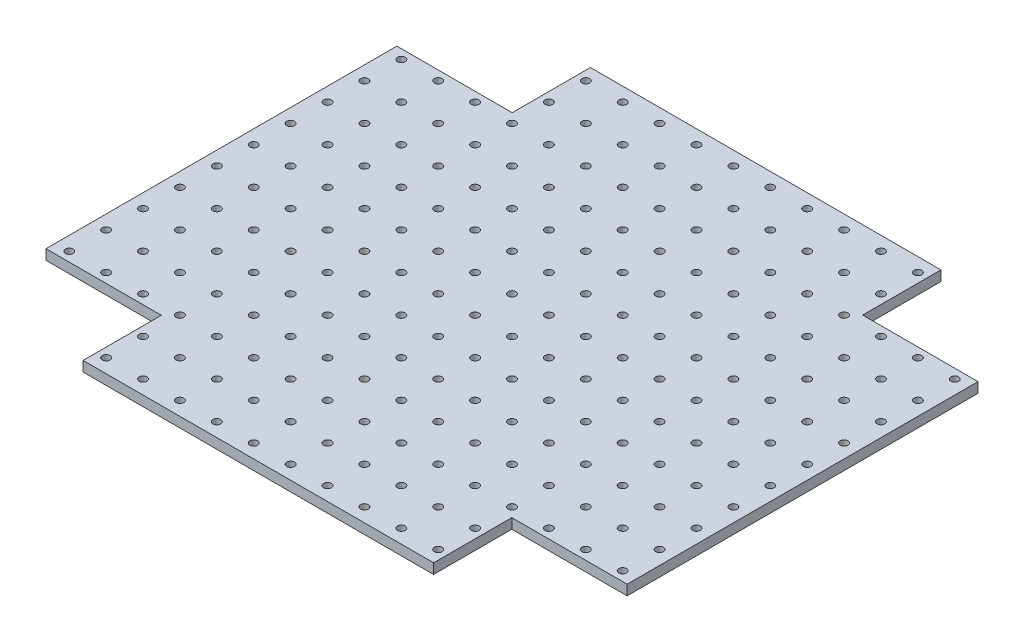
SolidWorks part; units mm, degrees
ref_plane "Front Plane" through (0, 0, 0) normal (0, 0, 1) x (1, 0, 0)
ref_plane "Top Plane" through (0, 0, 0) normal (0, 1, 0) x (1, 0, 0)
ref_plane "Right Plane" through (0, 0, 0) normal (1, 0, 0) x (0, 0, -1)
sketch "Sketch1" plane through (0, 0, 0) normal (0, 1, 0) x (1, 0, 0)
  line L0 (95, -95.1) -> (157.5, -95.1)
  line L1 (-157.5, 95.1) -> (-95, 95.1)
  line L2 (-157.5, 95.1) -> (-157.5, -95.1)
  line L3 (-157.5, -95.1) -> (-95, -95.1)
  line L4 (157.5, 95.1) -> (157.5, -95.1)
  line L5 (-157.5, 95.1) -> (157.5, -95.1) construction
  line L6 (-157.5, -95.1) -> (157.5, 95.1) construction
  line L7 (95, 137.5) -> (-95, 137.5)
  line L8 (95, 137.5) -> (95, 95.1)
  line L9 (95, -137.5) -> (-95, -137.5)
  line L10 (-95, 137.5) -> (-95, 95.1)
  line L11 (95, 137.5) -> (-95, -137.5) construction
  line L12 (95, -137.5) -> (-95, 137.5) construction
  line L13 (95, -95.1) -> (95, -137.5)
  line L14 (-95, -95.1) -> (-95, -137.5)
  line L15 (95, 95.1) -> (157.5, 95.1)
  point P0 (0, 0)
  point P6 (0, 0)
  dimension "D1" = 315
  dimension "D2" = 42.4
  dimension "D3" = 275
  dimension "D4" = 190
extrude "Boss-Extrude1" add sketch "Sketch1" along normal blind 5.4864
sketch "Sketch2" plane through (0, 5.4864, 0) normal (0, 1, 0) x (1, 0, 0)
  line L0 (0, 0) -> (150, 0) construction
  line L1 (150, 0) -> (150, -130) construction
  line L2 (150, -130) -> (130, -130) construction
  line L3 (150, -110) -> (130, -110) construction
  line L4 (150, -90) -> (130, -90) construction
  line L5 (150, -70) -> (130, -70) construction
  line L6 (150, -50) -> (130, -50) construction
  line L7 (150, -30) -> (130, -30) construction
  line L8 (150, -10) -> (130, -10) construction
  line L9 (150, 10) -> (130, 10) construction
  line L10 (150, 30) -> (130, 30) construction
  line L11 (150, 50) -> (130, 50) construction
  line L12 (150, 70) -> (130, 70) construction
  line L13 (150, 90) -> (130, 90) construction
  line L14 (150, 110) -> (130, 110) construction
  line L15 (150, -130) -> (150, -110) construction
  line L16 (150, 130) -> (130, 130) construction
  line L17 (150, 150) -> (130, 150) construction
  circle A0 centre (150, -130) radius 2.1 construction
  circle A1 centre (130, -130) radius 2.1 construction
  circle A2 centre (110, -130) radius 2.1 construction
  circle A3 centre (90, -130) radius 2.1
  circle A4 centre (70, -130) radius 2.1
  circle A5 centre (50, -130) radius 2.1
  circle A6 centre (30, -130) radius 2.1
  circle A7 centre (10, -130) radius 2.1
  circle A8 centre (-10, -130) radius 2.1
  circle A9 centre (-30, -130) radius 2.1
  circle A10 centre (-50, -130) radius 2.1
  circle A11 centre (-70, -130) radius 2.1
  circle A12 centre (-90, -130) radius 2.1
  circle A13 centre (-110, -130) radius 2.1
  circle A14 centre (-130, -130) radius 2.1 construction
  circle A15 centre (-150, -130) radius 2.1 construction
  circle A17 centre (150, -110) radius 2.1 construction
  circle A18 centre (130, -110) radius 2.1 construction
  circle A19 centre (110, -110) radius 2.1 construction
  circle A20 centre (90, -110) radius 2.1
  circle A21 centre (70, -110) radius 2.1
  circle A22 centre (50, -110) radius 2.1
  circle A23 centre (30, -110) radius 2.1
  circle A24 centre (10, -110) radius 2.1
  circle A25 centre (-10, -110) radius 2.1
  circle A26 centre (-30, -110) radius 2.1
  circle A27 centre (-50, -110) radius 2.1
  circle A28 centre (-70, -110) radius 2.1
  circle A29 centre (-90, -110) radius 2.1
  circle A30 centre (-110, -110) radius 2.1
  circle A31 centre (-130, -110) radius 2.1 construction
  circle A32 centre (-150, -110) radius 2.1 construction
  circle A34 centre (150, -90) radius 2.1
  circle A35 centre (130, -90) radius 2.1
  circle A36 centre (110, -90) radius 2.1
  circle A37 centre (90, -90) radius 2.1
  circle A38 centre (70, -90) radius 2.1
  circle A39 centre (50, -90) radius 2.1
  circle A40 centre (30, -90) radius 2.1
  circle A41 centre (10, -90) radius 2.1
  circle A42 centre (-10, -90) radius 2.1
  circle A43 centre (-30, -90) radius 2.1
  circle A44 centre (-50, -90) radius 2.1
  circle A45 centre (-70, -90) radius 2.1
  circle A46 centre (-90, -90) radius 2.1
  circle A47 centre (-110, -90) radius 2.1
  circle A48 centre (-130, -90) radius 2.1
  circle A49 centre (-150, -90) radius 2.1
  circle A51 centre (150, -70) radius 2.1
  circle A52 centre (130, -70) radius 2.1
  circle A53 centre (110, -70) radius 2.1
  circle A54 centre (90, -70) radius 2.1
  circle A55 centre (70, -70) radius 2.1
  circle A56 centre (50, -70) radius 2.1
  circle A57 centre (30, -70) radius 2.1
  circle A58 centre (10, -70) radius 2.1
  circle A59 centre (-10, -70) radius 2.1
  circle A60 centre (-30, -70) radius 2.1
  circle A61 centre (-50, -70) radius 2.1
  circle A62 centre (-70, -70) radius 2.1
  circle A63 centre (-90, -70) radius 2.1
  circle A64 centre (-110, -70) radius 2.1
  circle A65 centre (-130, -70) radius 2.1
  circle A66 centre (-150, -70) radius 2.1
  circle A68 centre (150, -50) radius 2.1
  circle A69 centre (130, -50) radius 2.1
  circle A70 centre (110, -50) radius 2.1
  circle A71 centre (90, -50) radius 2.1
  circle A72 centre (70, -50) radius 2.1
  circle A73 centre (50, -50) radius 2.1
  circle A74 centre (30, -50) radius 2.1
  circle A75 centre (10, -50) radius 2.1
  circle A76 centre (-10, -50) radius 2.1
  circle A77 centre (-30, -50) radius 2.1
  circle A78 centre (-50, -50) radius 2.1
  circle A79 centre (-70, -50) radius 2.1
  circle A80 centre (-90, -50) radius 2.1
  circle A81 centre (-110, -50) radius 2.1
  circle A82 centre (-130, -50) radius 2.1
  circle A83 centre (-150, -50) radius 2.1
  circle A85 centre (150, -30) radius 2.1
  circle A86 centre (130, -30) radius 2.1
  circle A87 centre (110, -30) radius 2.1
  circle A88 centre (90, -30) radius 2.1
  circle A89 centre (70, -30) radius 2.1
  circle A90 centre (50, -30) radius 2.1
  circle A91 centre (30, -30) radius 2.1
  circle A92 centre (10, -30) radius 2.1
  circle A93 centre (-10, -30) radius 2.1
  circle A94 centre (-30, -30) radius 2.1
  circle A95 centre (-50, -30) radius 2.1
  circle A96 centre (-70, -30) radius 2.1
  circle A97 centre (-90, -30) radius 2.1
  circle A98 centre (-110, -30) radius 2.1
  circle A99 centre (-130, -30) radius 2.1
  circle A100 centre (-150, -30) radius 2.1
  circle A102 centre (150, -10) radius 2.1
  circle A103 centre (130, -10) radius 2.1
  circle A104 centre (110, -10) radius 2.1
  circle A105 centre (90, -10) radius 2.1
  circle A106 centre (70, -10) radius 2.1
  circle A107 centre (50, -10) radius 2.1
  circle A108 centre (30, -10) radius 2.1
  circle A109 centre (10, -10) radius 2.1
  circle A110 centre (-10, -10) radius 2.1
  circle A111 centre (-30, -10) radius 2.1
  circle A112 centre (-50, -10) radius 2.1
  circle A113 centre (-70, -10) radius 2.1
  circle A114 centre (-90, -10) radius 2.1
  circle A115 centre (-110, -10) radius 2.1
  circle A116 centre (-130, -10) radius 2.1
  circle A117 centre (-150, -10) radius 2.1
  circle A119 centre (150, 10) radius 2.1
  circle A120 centre (130, 10) radius 2.1
  circle A121 centre (110, 10) radius 2.1
  circle A122 centre (90, 10) radius 2.1
  circle A123 centre (70, 10) radius 2.1
  circle A124 centre (50, 10) radius 2.1
  circle A125 centre (30, 10) radius 2.1
  circle A126 centre (10, 10) radius 2.1
  circle A127 centre (-10, 10) radius 2.1
  circle A128 centre (-30, 10) radius 2.1
  circle A129 centre (-50, 10) radius 2.1
  circle A130 centre (-70, 10) radius 2.1
  circle A131 centre (-90, 10) radius 2.1
  circle A132 centre (-110, 10) radius 2.1
  circle A133 centre (-130, 10) radius 2.1
  circle A134 centre (-150, 10) radius 2.1
  circle A136 centre (150, 30) radius 2.1
  circle A137 centre (130, 30) radius 2.1
  circle A138 centre (110, 30) radius 2.1
  circle A139 centre (90, 30) radius 2.1
  circle A140 centre (70, 30) radius 2.1
  circle A141 centre (50, 30) radius 2.1
  circle A142 centre (30, 30) radius 2.1
  circle A143 centre (10, 30) radius 2.1
  circle A144 centre (-10, 30) radius 2.1
  circle A145 centre (-30, 30) radius 2.1
  circle A146 centre (-50, 30) radius 2.1
  circle A147 centre (-70, 30) radius 2.1
  circle A148 centre (-90, 30) radius 2.1
  circle A149 centre (-110, 30) radius 2.1
  circle A150 centre (-130, 30) radius 2.1
  circle A151 centre (-150, 30) radius 2.1
  circle A153 centre (150, 50) radius 2.1
  circle A154 centre (130, 50) radius 2.1
  circle A155 centre (110, 50) radius 2.1
  circle A156 centre (90, 50) radius 2.1
  circle A157 centre (70, 50) radius 2.1
  circle A158 centre (50, 50) radius 2.1
  circle A159 centre (30, 50) radius 2.1
  circle A160 centre (10, 50) radius 2.1
  circle A161 centre (-10, 50) radius 2.1
  circle A162 centre (-30, 50) radius 2.1
  circle A163 centre (-50, 50) radius 2.1
  circle A164 centre (-70, 50) radius 2.1
  circle A165 centre (-90, 50) radius 2.1
  circle A166 centre (-110, 50) radius 2.1
  circle A167 centre (-130, 50) radius 2.1
  circle A168 centre (-150, 50) radius 2.1
  circle A170 centre (150, 70) radius 2.1
  circle A171 centre (130, 70) radius 2.1
  circle A172 centre (110, 70) radius 2.1
  circle A173 centre (90, 70) radius 2.1
  circle A174 centre (70, 70) radius 2.1
  circle A175 centre (50, 70) radius 2.1
  circle A176 centre (30, 70) radius 2.1
  circle A177 centre (10, 70) radius 2.1
  circle A178 centre (-10, 70) radius 2.1
  circle A179 centre (-30, 70) radius 2.1
  circle A180 centre (-50, 70) radius 2.1
  circle A181 centre (-70, 70) radius 2.1
  circle A182 centre (-90, 70) radius 2.1
  circle A183 centre (-110, 70) radius 2.1
  circle A184 centre (-130, 70) radius 2.1
  circle A185 centre (-150, 70) radius 2.1
  circle A187 centre (150, 90) radius 2.1
  circle A188 centre (130, 90) radius 2.1
  circle A189 centre (110, 90) radius 2.1
  circle A190 centre (90, 90) radius 2.1
  circle A191 centre (70, 90) radius 2.1
  circle A192 centre (50, 90) radius 2.1
  circle A193 centre (30, 90) radius 2.1
  circle A194 centre (10, 90) radius 2.1
  circle A195 centre (-10, 90) radius 2.1
  circle A196 centre (-30, 90) radius 2.1
  circle A197 centre (-50, 90) radius 2.1
  circle A198 centre (-70, 90) radius 2.1
  circle A199 centre (-90, 90) radius 2.1
  circle A200 centre (-110, 90) radius 2.1
  circle A201 centre (-130, 90) radius 2.1
  circle A202 centre (-150, 90) radius 2.1
  circle A204 centre (150, 110) radius 2.1
  circle A205 centre (130, 110) radius 2.1
  circle A206 centre (110, 110) radius 2.1
  circle A207 centre (90, 110) radius 2.1
  circle A208 centre (70, 110) radius 2.1
  circle A209 centre (50, 110) radius 2.1
  circle A210 centre (30, 110) radius 2.1
  circle A211 centre (10, 110) radius 2.1
  circle A212 centre (-10, 110) radius 2.1
  circle A213 centre (-30, 110) radius 2.1
  circle A214 centre (-50, 110) radius 2.1
  circle A215 centre (-70, 110) radius 2.1
  circle A216 centre (-90, 110) radius 2.1
  circle A217 centre (-110, 110) radius 2.1
  circle A218 centre (-130, 110) radius 2.1
  circle A219 centre (-150, 110) radius 2.1
  circle A221 centre (150, 130) radius 2.1 construction
  circle A222 centre (130, 130) radius 2.1 construction
  circle A223 centre (110, 130) radius 2.1
  circle A224 centre (90, 130) radius 2.1
  circle A225 centre (70, 130) radius 2.1
  circle A226 centre (50, 130) radius 2.1
  circle A227 centre (30, 130) radius 2.1
  circle A228 centre (10, 130) radius 2.1
  circle A229 centre (-10, 130) radius 2.1
  circle A230 centre (-30, 130) radius 2.1
  circle A231 centre (-50, 130) radius 2.1
  circle A232 centre (-70, 130) radius 2.1
  circle A233 centre (-90, 130) radius 2.1
  circle A234 centre (-110, 130) radius 2.1
  circle A235 centre (-130, 130) radius 2.1 construction
  circle A236 centre (-150, 130) radius 2.1 construction
  circle A238 centre (150, 150) radius 2.1 construction
  circle A239 centre (130, 150) radius 2.1 construction
  circle A240 centre (110, 150) radius 2.1 construction
  circle A241 centre (90, 150) radius 2.1
  circle A242 centre (70, 150) radius 2.1
  circle A243 centre (50, 150) radius 2.1
  circle A244 centre (30, 150) radius 2.1
  circle A245 centre (10, 150) radius 2.1
  circle A246 centre (-10, 150) radius 2.1
  circle A247 centre (-30, 150) radius 2.1
  circle A248 centre (-50, 150) radius 2.1
  circle A249 centre (-70, 150) radius 2.1
  circle A250 centre (-90, 150) radius 2.1
  circle A251 centre (-110, 150) radius 2.1
  circle A252 centre (-130, 150) radius 2.1 construction
  circle A253 centre (-150, 150) radius 2.1 construction
  dimension "D3" = 4.2
  dimension "D1" = 150
  dimension "D2" = 130
  dimension "D5" = 20
  dimension "D7" = 20
  dimension "D4" = 16
  dimension "D6" = 15
extrude "Cut-Extrude1" cut sketch "Sketch2" against normal through all
